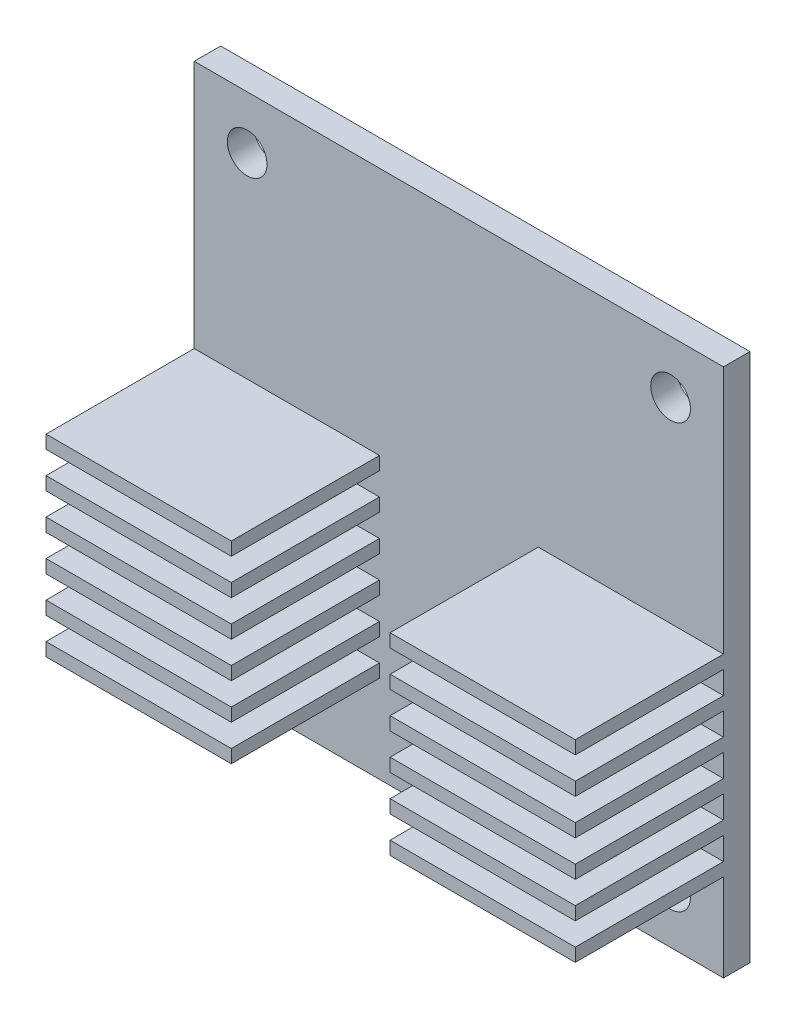
SolidWorks part; units mm, degrees
note: The reader was unsure of these and kept them because the rebuilt part matched: shared geometry of "Sketch1<3>".
ref_plane "Front Plane" through (0, 0, 0) normal (0, 0, 1) x (1, 0, 0)
ref_plane "Top Plane" through (0, 0, 0) normal (0, 1, 0) x (1, 0, 0)
ref_plane "Right Plane" through (0, 0, 0) normal (1, 0, 0) x (0, 0, -1)
sketch "Sketch1" plane through (0, 0, 0) normal (0, 0, 1) x (1, 0, 0)
  line L0 (41, 4.4837) -> (27, 4.4837)
  line L1 (41, 2.4837) -> (1, 2.4837)
  line L2 (41, 2.4837) -> (41, 42.4837)
  line L3 (41, 42.4837) -> (1, 42.4837)
  line L4 (1, 2.4837) -> (1, 42.4837)
  line L5 (21, 40.4837) -> (21, 4.4837) construction
  line L6 (41, 21.7785) -> (27, 21.7785) construction
  line L7 (41, 4.4837) -> (41, 40.4837)
  line L8 (27, 4.4837) -> (27, 40.4837)
  line L9 (15, 4.4837) -> (15, 40.4837)
  line L10 (1, 4.4837) -> (1, 40.4837)
  line L11 (25, 4.4837) -> (25, 40.4837)
  line L12 (17, 4.4837) -> (17, 40.4837)
  line L13 (41, 40.4837) -> (27, 40.4837)
  line L14 (41, 5.4837) -> (27, 5.4837)
  line L15 (41, 6.389) -> (27, 6.389)
  line L16 (41, 7.2943) -> (27, 7.2943)
  line L17 (41, 8.1995) -> (27, 8.1995)
  line L18 (41, 9.1048) -> (27, 9.1048)
  line L19 (41, 10.01) -> (27, 10.01)
  line L20 (41, 10.9153) -> (27, 10.9153)
  line L21 (41, 11.8206) -> (27, 11.8206)
  line L22 (41, 12.7258) -> (27, 12.7258)
  line L23 (41, 13.6311) -> (27, 13.6311)
  line L24 (41, 14.5364) -> (27, 14.5364)
  line L25 (41, 15.4416) -> (27, 15.4416)
  line L26 (41, 16.3469) -> (27, 16.3469)
  line L27 (41, 17.2522) -> (27, 17.2522)
  line L28 (41, 18.1574) -> (27, 18.1574)
  line L29 (41, 19.0627) -> (27, 19.0627)
  line L30 (41, 19.9679) -> (27, 19.9679)
  line L31 (41, 20.8732) -> (27, 20.8732)
  line L32 (41, 21.7785) -> (27, 21.7785)
  line L33 (41, 22.6837) -> (27, 22.6837)
  line L34 (41, 23.589) -> (27, 23.589)
  line L35 (41, 24.4943) -> (27, 24.4943)
  line L36 (41, 25.3995) -> (27, 25.3995)
  line L37 (41, 26.3048) -> (27, 26.3048)
  line L38 (41, 27.21) -> (27, 27.21)
  line L39 (41, 28.1153) -> (27, 28.1153)
  line L40 (41, 29.0206) -> (27, 29.0206)
  line L41 (41, 29.9258) -> (27, 29.9258)
  line L42 (41, 30.8311) -> (27, 30.8311)
  line L43 (41, 31.7364) -> (27, 31.7364)
  line L44 (41, 32.6416) -> (27, 32.6416)
  line L45 (41, 33.5469) -> (27, 33.5469)
  line L46 (41, 34.4522) -> (27, 34.4522)
  line L47 (41, 35.3574) -> (27, 35.3574)
  line L48 (41, 36.2627) -> (27, 36.2627)
  line L49 (41, 37.1679) -> (27, 37.1679)
  line L50 (41, 38.0732) -> (27, 38.0732)
  line L51 (46.6374, 3.6837) -> (46.6374, 4.6837) construction
  line L52 (45.6374, 5.4837) -> (-11.288, 5.4837) construction
  line L53 (45.6374, 4.4837) -> (-11.288, 4.4837) construction
  line L54 (25, 4.4837) -> (17, 4.4837)
  line L55 (25, 5.4837) -> (17, 5.4837)
  line L56 (25, 6.389) -> (17, 6.389)
  line L57 (25, 7.2943) -> (17, 7.2943)
  line L58 (25, 8.1995) -> (17, 8.1995)
  line L59 (25, 9.1048) -> (17, 9.1048)
  line L60 (25, 10.01) -> (17, 10.01)
  line L61 (25, 10.9153) -> (17, 10.9153)
  line L62 (25, 11.8206) -> (17, 11.8206)
  line L63 (25, 12.7258) -> (17, 12.7258)
  line L64 (25, 13.6311) -> (17, 13.6311)
  line L65 (25, 14.5364) -> (17, 14.5364)
  line L66 (25, 15.4416) -> (17, 15.4416)
  line L67 (25, 16.3469) -> (17, 16.3469)
  line L68 (25, 17.2522) -> (17, 17.2522)
  line L69 (25, 18.1574) -> (17, 18.1574)
  line L70 (25, 19.0627) -> (17, 19.0627)
  line L71 (25, 19.9679) -> (17, 19.9679)
  line L72 (25, 20.8732) -> (17, 20.8732)
  line L73 (25, 21.7785) -> (17, 21.7785) construction
  line L74 (25, 21.7785) -> (17, 21.7785)
  line L75 (25, 22.6837) -> (17, 22.6837)
  line L76 (25, 23.589) -> (17, 23.589)
  line L77 (25, 24.4943) -> (17, 24.4943)
  line L78 (25, 25.3995) -> (17, 25.3995)
  line L79 (25, 26.3048) -> (17, 26.3048)
  line L80 (25, 27.21) -> (17, 27.21)
  line L81 (25, 28.1153) -> (17, 28.1153)
  line L82 (25, 29.0206) -> (17, 29.0206)
  line L83 (25, 29.9258) -> (17, 29.9258)
  line L84 (25, 30.8311) -> (17, 30.8311)
  line L85 (25, 31.7364) -> (17, 31.7364)
  line L86 (25, 32.6416) -> (17, 32.6416)
  line L87 (25, 33.5469) -> (17, 33.5469)
  line L88 (25, 34.4522) -> (17, 34.4522)
  line L89 (25, 35.3574) -> (17, 35.3574)
  line L90 (25, 36.2627) -> (17, 36.2627)
  line L91 (25, 37.1679) -> (17, 37.1679)
  line L92 (25, 38.0732) -> (17, 38.0732)
  line L93 (25, 40.4837) -> (17, 40.4837)
  line L94 (15, 4.4837) -> (1, 4.4837)
  line L95 (15, 5.4837) -> (1, 5.4837)
  line L96 (15, 6.389) -> (1, 6.389)
  line L97 (15, 7.2943) -> (1, 7.2943)
  line L98 (15, 8.1995) -> (1, 8.1995)
  line L99 (15, 9.1048) -> (1, 9.1048)
  line L100 (15, 10.01) -> (1, 10.01)
  line L101 (15, 10.9153) -> (1, 10.9153)
  line L102 (15, 11.8206) -> (1, 11.8206)
  line L103 (15, 12.7258) -> (1, 12.7258)
  line L104 (15, 13.6311) -> (1, 13.6311)
  line L105 (15, 14.5364) -> (1, 14.5364)
  line L106 (15, 15.4416) -> (1, 15.4416)
  line L107 (15, 16.3469) -> (1, 16.3469)
  line L108 (15, 17.2522) -> (1, 17.2522)
  line L109 (15, 18.1574) -> (1, 18.1574)
  line L110 (15, 19.0627) -> (1, 19.0627)
  line L111 (15, 19.9679) -> (1, 19.9679)
  line L112 (15, 20.8732) -> (1, 20.8732)
  line L113 (15, 21.7785) -> (1, 21.7785) construction
  line L114 (15, 21.7785) -> (1, 21.7785)
  line L115 (15, 22.6837) -> (1, 22.6837)
  line L116 (15, 23.589) -> (1, 23.589)
  line L117 (15, 24.4943) -> (1, 24.4943)
  line L118 (15, 25.3995) -> (1, 25.3995)
  line L119 (15, 26.3048) -> (1, 26.3048)
  line L120 (15, 27.21) -> (1, 27.21)
  line L121 (15, 28.1153) -> (1, 28.1153)
  line L122 (15, 29.0206) -> (1, 29.0206)
  line L123 (15, 29.9258) -> (1, 29.9258)
  line L124 (15, 30.8311) -> (1, 30.8311)
  line L125 (15, 31.7364) -> (1, 31.7364)
  line L126 (15, 32.6416) -> (1, 32.6416)
  line L127 (15, 33.5469) -> (1, 33.5469)
  line L128 (15, 34.4522) -> (1, 34.4522)
  line L129 (15, 35.3574) -> (1, 35.3574)
  line L130 (15, 36.2627) -> (1, 36.2627)
  line L131 (15, 37.1679) -> (1, 37.1679)
  line L132 (15, 38.0732) -> (1, 38.0732)
  line L133 (15, 40.4837) -> (1, 40.4837)
  point P48 (21, 21.7785)
  dimension "D1" = 2
  dimension "D2" = 2
  dimension "D3" = 0
  dimension "D4" = 0
  dimension "D5" = 2
  dimension "D6" = 2
  dimension "D7" = 14
  dimension "D8" = 14
  dimension "D10" = 1
  dimension "D9" = 1
extrude "Boss-Extrude1" add sketch "Sketch1" along normal blind 2 contours L1 L4 L3 L2
extrude "Extrude-Thin1" add sketch "Sketch1<3>" along normal blind 11.2 from surface at 2 thin contours L33 | L30 | L111 | L115 | L27 | L24 | L108 | L105 | L21 | L102 | L18 | L99
sketch "Sketch1<3>" plane through (0, 0, 0) normal (0, 0, 1) x (1, 0, 0) same geometry as "Sketch1"
sketch "Sketch3" plane through (0, 0, 0) normal (0, 0, -1) x (-1, 0, 0)
  line L1 (-21, 2.4837) -> (-21, 42.4837) construction
  line L2 (-5, 38.4837) -> (-37, 38.4837) construction
  line L3 (-5, 38.4837) -> (-5, 6.4837) construction
  line L4 (-5, 6.4837) -> (-37, 6.4837) construction
  line L5 (-37, 38.4837) -> (-37, 6.4837) construction
  line L6 (-21, 6.4837) -> (-21, 38.4837) construction
  line L7 (-5, 22.4837) -> (-37, 22.4837) construction
  line L8 (-41, 2.4837) -> (-1, 2.4837) construction
  line L9 (-41, 42.4837) -> (-1, 42.4837) construction
  line L10 (-41, 22.4837) -> (-1, 22.4837) construction
  line L11 (-41, 2.4837) -> (-41, 42.4837) construction
  line L12 (-1, 2.4837) -> (-1, 42.4837) construction
  circle A0 centre (-37, 6.4837) radius 1.5
  circle A1 centre (-5, 6.4837) radius 1.5
  circle A2 centre (-5, 38.4837) radius 1.5
  circle A3 centre (-37, 38.4837) radius 1.5
  point P141 (-21, 22.4837)
  dimension "D1" = 3
  dimension "D4" = 3
  dimension "D5" = 3
  dimension "D6" = 3
  dimension "D2" = 32
  dimension "D3" = 32
extrude "Cut-Extrude1" cut sketch "Sketch3" along direction (0, 0, 1) on the side against the normal up to vertex (13.2 mm away) from vertex at 0 contours A0
pattern_linear "LPattern1" count 2 spacing 32 along (-1, 0, 0) count 2 spacing 32 along (0, 1, 0) of "Cut-Extrude1"
